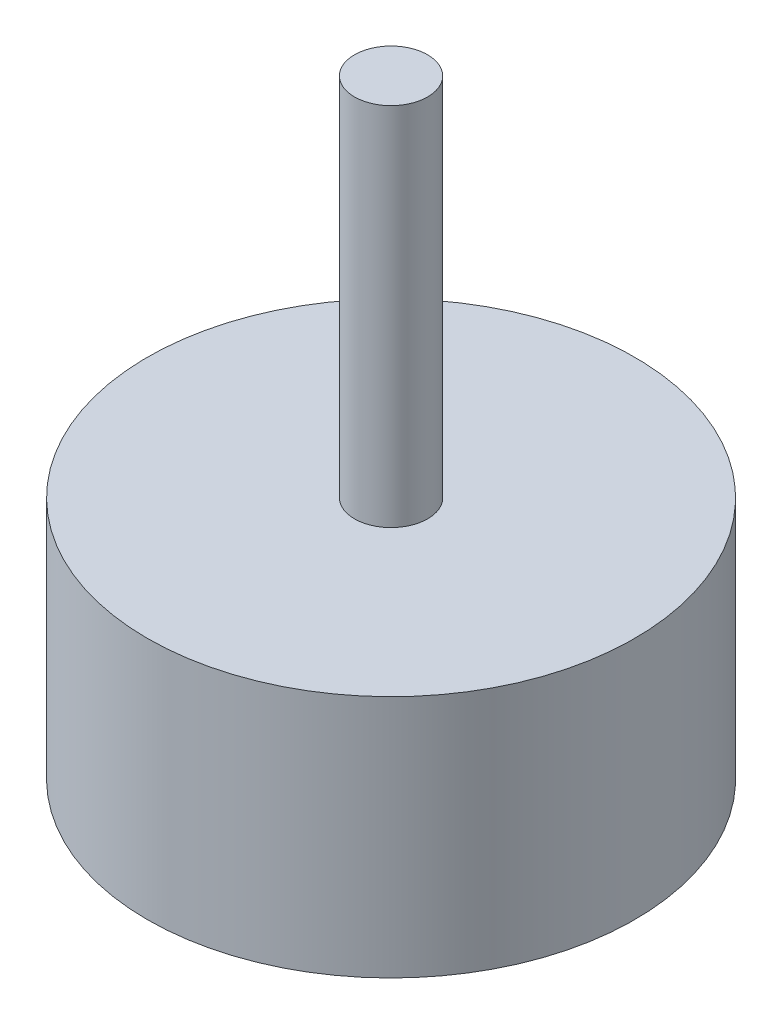
SolidWorks part; units mm, degrees
ref_plane "Front Plane" through (0, 0, 0) normal (0, 0, 1) x (1, 0, 0)
ref_plane "Top Plane" through (0, 0, 0) normal (0, 1, 0) x (1, 0, 0)
ref_plane "Right Plane" through (0, 0, 0) normal (1, 0, 0) x (0, 0, -1)
sketch "Sketch1" plane through (0, 0, 0) normal (0, 1, 0) x (1, 0, 0)
  circle A0 centre (0, 0) radius 10
  dimension "D1" = 20
extrude "Boss-Extrude1" add sketch "Sketch1" along normal blind 10
sketch "Sketch2" plane through (0, 10, 0) normal (0, 1, 0) x (1, 0, 0)
  circle A0 centre (0, 0) radius 1.5
  dimension "D1" = 3
extrude "Boss-Extrude2" add sketch "Sketch2" along normal blind 15
sketch "Sketch3" plane through (0, 0, 0) normal (0, -1, 0) x (1, 0, 0)
  line L1 (7, 0) -> (3.5, 6.0622)
  line L2 (3.5, 6.0622) -> (-3.5, 6.0622)
  line L3 (-3.5, 6.0622) -> (-7, 0)
  line L4 (-7, 0) -> (-3.5, -6.0622)
  line L5 (-3.5, -6.0622) -> (3.5, -6.0622)
  line L6 (3.5, -6.0622) -> (7, 0)
  circle A0 centre (0, 0) radius 6.0622 construction
  dimension "D1" = 7
extrude "Cut-Extrude1" cut sketch "Sketch3" against normal blind 8
ref_axis "Axis1" through (0, 10, 0) along (0, -1, 0)
